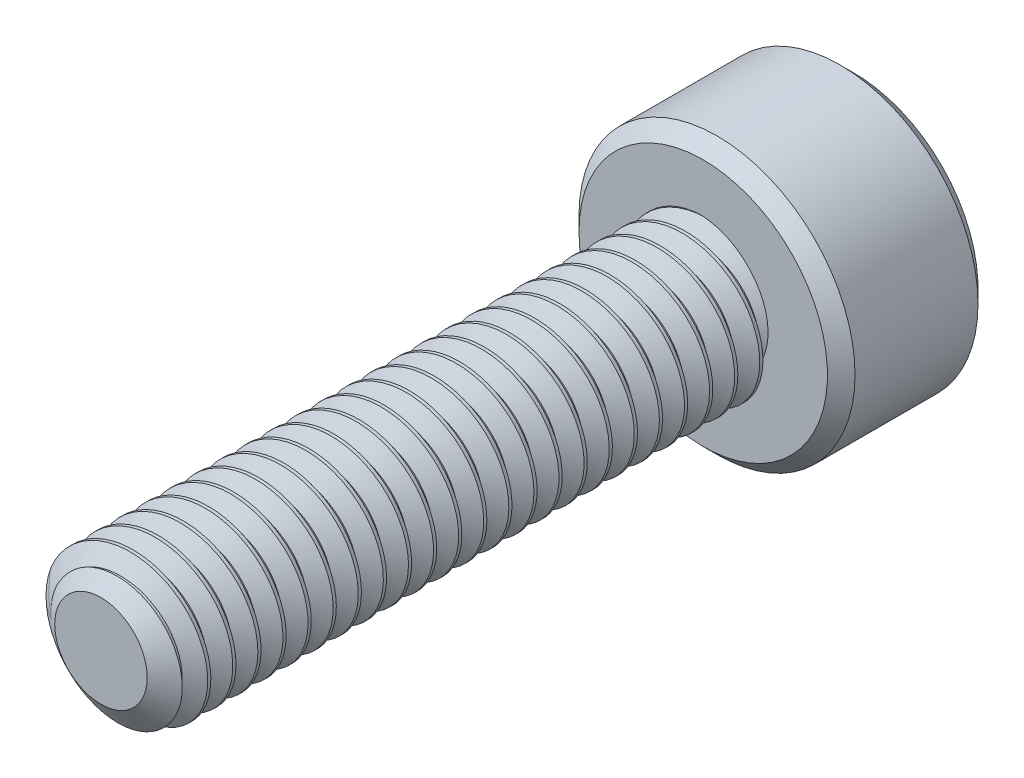
SolidWorks part; units mm, degrees
other "DetailItem1"
ref_plane "Front Plane" through (0, 0, 0) normal (0, 0, 1) x (1, 0, 0)
ref_plane "Top Plane" through (0, 0, 0) normal (0, 1, 0) x (1, 0, 0)
ref_plane "Right Plane" through (0, 0, 0) normal (1, 0, 0) x (0, 0, -1)
sketch "Sketch1" plane through (0, 0, 0) normal (0, 0, 1) x (1, 0, 0)
  circle A0 centre (0, 0) radius 1.5
  dimension "OD" = 3
extrude "Extrude1" add sketch "Sketch1" against normal blind 12
sketch "Sketch2" plane through (0, 0, 0) normal (0, 0, 1) x (1, 0, 0)
  circle A0 centre (0, 0) radius 1.5 construction
  circle A1 centre (0, 0) radius 1.5
curve "Helix/Spiral1" pitch 0.5 height 12.5 turns 25 parameters "pitch"=0.5
sketch "Sketch3" plane through (0, 0, 0) normal (1, 0, 0) x (0, 0, -1)
  line L0 (-0.4375, 1.5) -> (-0.25, 1.1752)
  line L1 (-0.25, 1.1752) -> (-0.1875, 1.1752)
  line L2 (-0.1875, 1.1752) -> (0, 1.5)
  line L3 (-0.4375, 1.5) -> (0, 1.5)
  line L4 (-0.2187, 1.5) -> (-0.2188, 1.1752) construction
  line L5 (-0.3438, 1.3376) -> (-0.0938, 1.3376) construction
  line L6 (0, 1.5) -> (0, -1.5) construction
  dimension "D1" = 0.0625
  dimension "D2" = 0.25
  dimension "D3" = 60
sweep "Cut-Sweep1" cut profiles "Sketch3" path "Helix/Spiral1"
sketch "Sketch4" plane through (0, 0, 0) normal (1, 0, 0) x (0, 0, -1)
  line L0 (0.4053, 1.5) -> (0, 0.9212)
  line L1 (0, 0.9212) -> (0, 1.5)
  line L2 (0.4053, 1.5) -> (0, 1.5)
  line L3 (-0.4375, 1.5) -> (0, 1.5) construction
  line L4 (0, 0) -> (7.0209, 0) construction
  dimension "D1" = 55
  dimension "D2" = 0.254
revolve "Cut-Revolve1" cut sketch "Sketch4" angle 360 about L4
sketch "Sketch6" plane through (0, 0, -12) normal (0, 0, -1) x (-1, 0, 0)
  circle A0 centre (0, 0) radius 2.75
  dimension "head dia" = 5.5
extrude "Extrude2" add sketch "Sketch6" along normal blind 3
sketch "Sketch7" plane through (0, 0, -15) normal (0, 0, -1) x (-1, 0, 0)
  line L1 (0, 1.4434) -> (-1.25, 0.7217)
  line L2 (-1.25, 0.7217) -> (-1.25, -0.7217)
  line L3 (-1.25, -0.7217) -> (0, -1.4434)
  line L4 (0, -1.4434) -> (1.25, -0.7217)
  line L5 (1.25, -0.7217) -> (1.25, 0.7217)
  line L6 (1.25, 0.7217) -> (0, 1.4434)
  circle A0 centre (0, 0) radius 1.25 construction
  dimension "hex dia" = 2.5
extrude "Cut-Extrude1" cut sketch "Sketch7" against normal blind 1.875
sketch "Sketch8" plane through (0, 0, -15) normal (0, 0, -1) x (-1, 0, 0)
  circle A0 centre (0, 0) radius 1.4434
extrude "Cut-Extrude2" cut sketch "Sketch8" against normal through all draft 45
chamfer "Chamfer1" distance 0.275 angle 45 2 edges at (-2.75, 0, -15) (-2.75, 0, -12)
sketch "Sketch10" plane through (0, 0, -12) normal (0, 0, 1) x (1, 0, 0)
  circle A1 centre (0, 0) radius 1.5
  circle A2 centre (0, 0) radius 1.5
  dimension "D1" = 0
ref_plane "Plane1" through (0, 0, 0) normal (0, 0, 1) x (1, 0, 0)
extrude "partial thread" [suppressed] add sketch "Sketch10" along normal up to surface (4 mm away) separate body
chamfer "Chamfer2" [suppressed] distance 0.06 angle 45
combine bodies "Combine1" [suppressed] operation type add bodies to combine 107 108
sketch "Sketch9" plane through (0, 0, 0) normal (1, 0, 0) x (0, 0, -1)
  line L0 (0, 1.5) -> (0, -1.5) construction
  line L1 (1.25, 1.5) -> (1.25, -1.5) construction
  dimension "D1" = 1.25
equation "\"D3@Helix/Spiral1\" = \"screw length@Extrude1\"+\"pitch@Helix/Spiral1\""
equation "\"D1@Sketch3\" = \"pitch@Helix/Spiral1\"*.125"
equation "\"D2@Sketch3\" = \"pitch@Helix/Spiral1\"*.5"
equation "\"D1@Cut-Extrude1\" = \"hex dia@Sketch7\"*.75"
equation "\"D1@Chamfer1\" = \"head dia@Sketch6\"*.05"
equation "\"D1@Sketch9\" = \"pitch@Helix/Spiral1\"*2.5"
equation "\"D1@Chamfer2\"=\"OD@Sketch1\"*.02"
